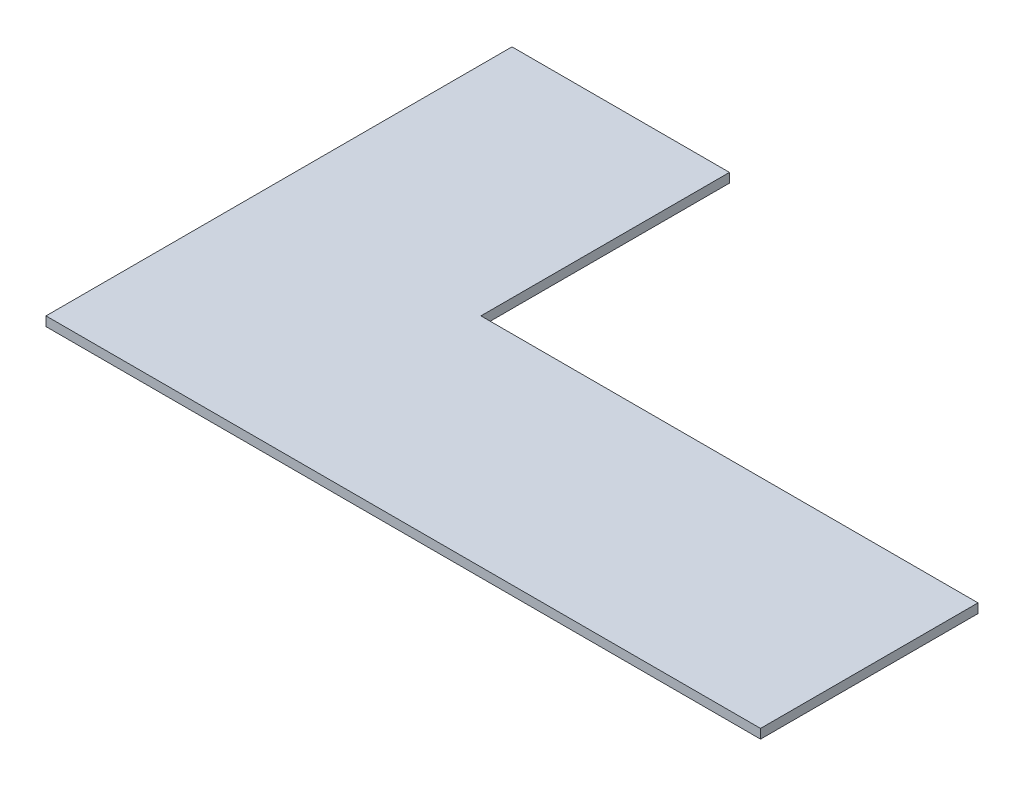
SolidWorks part; units mm, degrees
ref_plane "Front Plane" through (0, 0, 0) normal (0, 0, 1) x (1, 0, 0)
ref_plane "Top Plane" through (0, 0, 0) normal (0, 1, 0) x (1, 0, 0)
ref_plane "Right Plane" through (0, 0, 0) normal (1, 0, 0) x (0, 0, -1)
sketch "Sketch1" plane through (0, 0, 0) normal (0, 1, 0) x (1, 0, 0)
  line L0 (-115, -35) -> (115, -35)
  line L2 (-115, -35) -> (-115, 35)
  line L4 (115, -35) -> (115, 35)
  line L5 (-115, -35) -> (115, 35) construction
  line L6 (-115, 35) -> (115, -35) construction
  line L15 (-45, 35) -> (115, 35)
  line L17 (-115, 35) -> (-115, 115)
  line L18 (-115, 115) -> (-45, 115)
  line L19 (-45, 35) -> (-45, 115)
  point P0 (0, 0)
  dimension "D1" = 230
  dimension "D2" = 70
  dimension "D3" = 70
  dimension "D4" = 150
extrude "Boss-Extrude1" add sketch "Sketch1" along normal blind 3
